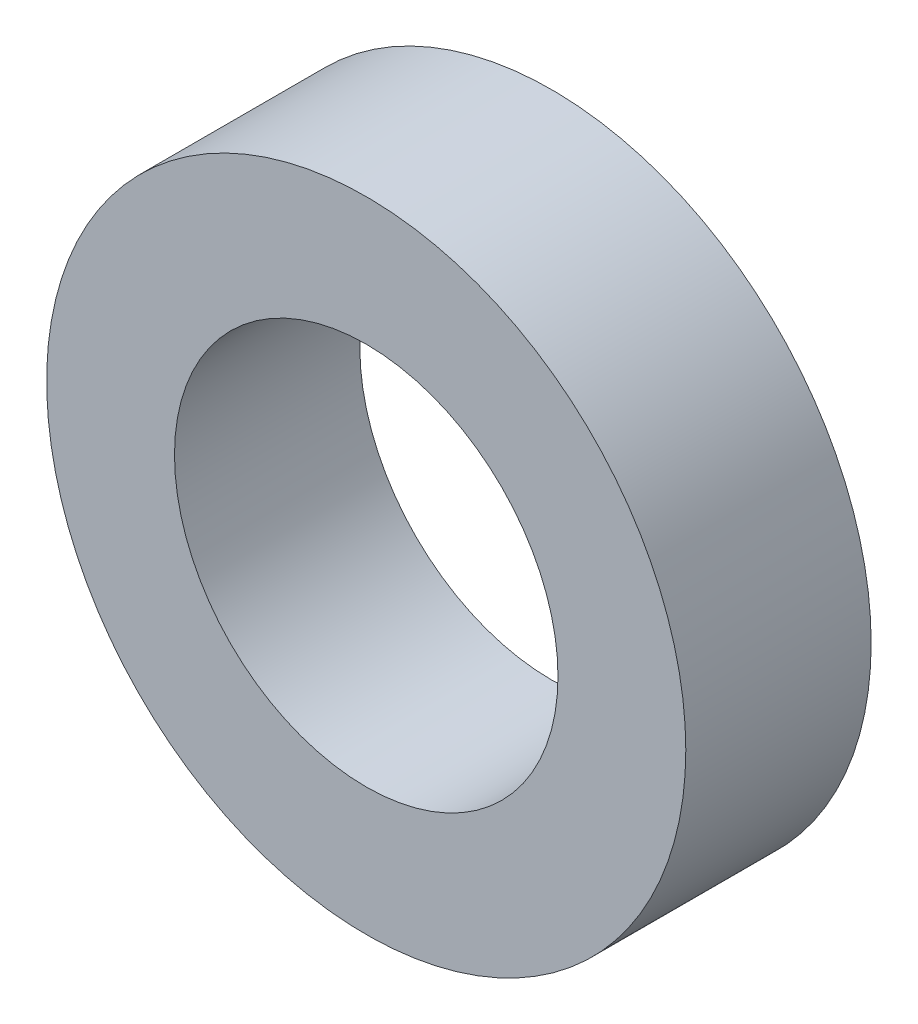
SolidWorks part; units mm, degrees
ref_plane "Front Plane" through (0, 0, 0) normal (0, 0, 1) x (1, 0, 0)
ref_plane "Top Plane" through (0, 0, 0) normal (0, 1, 0) x (1, 0, 0)
ref_plane "Right Plane" through (0, 0, 0) normal (1, 0, 0) x (0, 0, -1)
sketch "Sketch1" plane through (0, 0, 0) normal (0, 0, 1) x (1, 0, 0)
  circle A0 centre (0, 0) radius 3
  circle A1 centre (0, 0) radius 5
  dimension "D1" = 6
  dimension "D2" = 10
extrude "Boss-Extrude1" add sketch "Sketch1" along normal blind 2.9
equation "\"smallPulleyTeeth\"= 15"
equation "\"largePulleyTeeth\"= 30"
equation "\"eighthThick\"= 2.9mm"
equation "\"sixteenthThick\" = 1.7mm"
equation "\"quarterThick\"=5.9mm"
equation "\"OD\" = 145mm"
equation "\"puckAngle\" = 60.5deg"
equation "\"puckDiam\" = 76.5mm"
equation "\"axlePress\" = 5.9mm"
equation "\"press\" = 0.2mm"
equation "\"wheelClear\" = 0.3mm"
equation "\"10-32clear\" = 4.5mm"
equation "\"6-32clear\" = 3.3mm"
equation "\"8-32clear\" = 4.0mm"
equation "\"D1@Boss-Extrude1\"=\"eighthThick\""
